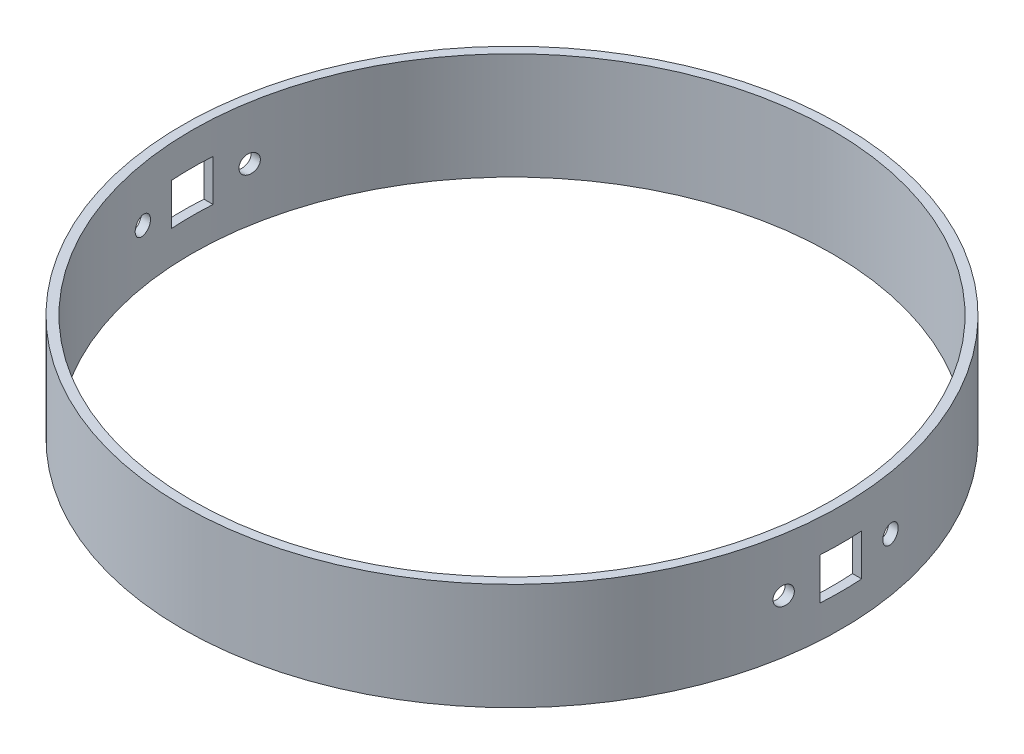
SolidWorks part; units mm, degrees
material "A-Glass Fiber"
ref_plane "Front Plane" through (0, 0, 0) normal (0, 0, 1) x (1, 0, 0)
ref_plane "Top Plane" through (0, 0, 0) normal (0, 1, 0) x (1, 0, 0)
ref_plane "Right Plane" through (0, 0, 0) normal (1, 0, 0) x (0, 0, -1)
sketch "Sketch1" plane through (0, 0, 0) normal (0, 1, 0) x (1, 0, 0)
  circle A0 centre (0, 0) radius 78.359
  circle A1 centre (0, 0) radius 76.1746
  dimension "D1" = 156.718
  dimension "D2" = 152.3492
extrude "Boss-Extrude1" add sketch "Sketch1" along normal blind 25.4
sketch "Sketch2" plane through (0, 0, 0) normal (1, 0, 0) x (0, 0, -1)
  line L0 (-78.359, 0) -> (78.359, 0) construction
  line L7 (0, 12.7) -> (0, 14.52) construction
  line L12 (4.953, 7.747) -> (-4.953, 7.747)
  line L13 (0, 25.4) -> (0, 0) construction
  line L14 (76.1746, 25.4) -> (-76.1746, 25.4) construction
  line L15 (-78.359, 0) -> (78.359, 0)
  line L16 (76.1746, 25.4) -> (-76.1746, 25.4)
  line L17 (-28.7231, 12.7) -> (26.1298, 12.7) construction
  line L25 (4.953, 7.747) -> (4.953, 17.653)
  line L26 (4.953, 17.653) -> (-4.953, 17.653)
  line L27 (-4.953, 7.747) -> (-4.953, 17.653)
  line L28 (4.953, 7.747) -> (-4.953, 17.653) construction
  line L29 (4.953, 17.653) -> (-4.953, 7.747) construction
  circle A0 centre (-12.7, 12.7) radius 2.1831
  circle A1 centre (12.7, 12.7) radius 2.1831
  point P0 (0, 9.85)
  point P14 (0, 3.175)
  point P27 (0, 12.7)
  dimension "D4" = 9.906
  dimension "D8" = 4.3663
  dimension "D1" = 12.7
  dimension "D5" = 9.906
extrude "Cut-Extrude1" cut sketch "Sketch2" along normal through all both and the other way through all contours L25 L12 L27 L26 | A1 | A0
ref_plane "Plane1" through (0, 0, 0) normal (0.9973, 0, 0.0728) x (0, -1, 0)
sketch "Sketch5" plane through (0, 0, 0) normal (0.9973, 0, 0.0728) x (0, -1, 0)
  line L0 (-13.35, 0.7076) -> (-13.35, 10.681) construction
  circle A0 centre (-20.335, 0) radius 2.75
  dimension "D1" = 5.5
  dimension "D2" = 6.985
extrude "Cut-Extrude2" [suppressed] cut sketch "Sketch5" along normal through all
ref_plane "Plane2" through (0, 12.7, 0) normal (0, 1, 0) x (1, 0, 0)
pattern_circular "CirPattern1" [suppressed] count 2 every 8.407 of bodies 104
mirror "Mirror2" about plane through (0, 0, 0) normal (1, 0, 0) of "Cut-Extrude1", "CirPattern1", "Boss-Extrude1" second plane through (0, 12.7, 0) second plane normal (0, 1, 0)
sketch "Sketch8" plane through (0, 0, 0) normal (1, 0, 0) x (0, 0, -1)
  line L0 (0, 25.4) -> (0, 0) construction
  line L1 (5, 15.225) -> (-5, 15.225)
  line L2 (5, 15.225) -> (5, 22.225)
  line L3 (5, 22.225) -> (-5, 22.225)
  line L4 (-5, 15.225) -> (-5, 22.225)
  line L5 (5, 15.225) -> (-5, 22.225) construction
  line L6 (5, 22.225) -> (-5, 15.225) construction
  line L8 (78.359, 25.4) -> (-78.359, 25.4) construction
  circle A0 centre (0, 6.335) radius 2.75
  point P0 (0, 18.725)
  dimension "D4" = 5.5
  dimension "D1" = 10
  dimension "D2" = 7
  dimension "D3" = 3.175
  dimension "D5" = 8.89
extrude "Cut-Extrude3" [suppressed] cut sketch "Sketch8" against normal through all
sketch "Sketch9" [suppressed] plane through (0, 0, 0) normal (0.9973, 0, 0.0728) x (0, -1, 0)
  line L0 (-15.225, -10.6344) -> (-15.225, -10.681) construction
  line L1 (-25.4, 0) -> (0, 0) construction
  circle A0 centre (-11.415, 0) radius 2.75
  dimension "D1" = 5.5
  dimension "D2" = 3.81
extrude "Cut-Extrude4" [suppressed] cut sketch "Sketch9" against normal through all
pattern_circular "CirPattern2" [suppressed] count 2 every 8.41 of bodies 109
equation "\"Mid_Tube_Length\"= 1in"
equation "\"Bodytube_OD\" = 6.17in"
equation "\"Bodytube_ID\" = 5.998in"
equation "\"D1@Sketch1\"=\"Bodytube_OD\""
equation "\"D2@Sketch1\"= \"Bodytube_ID\""
equation "\"Camera_Cutout_Width\"=10mm"
equation "\"Camera_Cutout_Height\"=7mm"
equation "\"Fwd_Tube_Length\" = 40in"
equation "\"BKHD_Screw_Diam\"= 3.5mm"
equation "\"Fwd_BKHD_From_Top\" = 18in"
equation "\"Shear_Screw_Diameter\" = 0.086in"
equation "\"Shear_Screw_Coupler_Location\" = 4.5in"
equation "\"Motor_OD\" = 4in"
equation "\"Mid_Coupler_Length\" = 13in"
equation "\"Aft_Section_Length\"= 39in"
equation "\"AB_Coupler_OD_Length\"= 1in"
equation "\"AB_Coupling_Section_Length\"= 0.375in"
equation "\"AB_Coupler_Length\"= \"AB_Coupler_OD_Length\" + \"AB_Coupling_Section_Length\" * 2"
equation "\"Cutout_Angle\" = 80"
equation "\"AB_Paddle_Height\" = 0.375in"
equation "\"AB_Coupler_Num_Screws\"= 4"
equation "\"AB_BKHD_Thickness\" = 0.375in"
equation "\"AB_Mount_From_Bottom\" = 23.175in"
equation "\"Num_Cutouts\" = 3"
equation "\"AB_Coupler_OD\"= 6.17in"
equation "\"AB_Coupler_ID\"= 5.75in"
equation "\"AB_Coupler_Surface_Diameter\"= 5.998in"
equation "\"AB_Coupling_Screw_Diameter\"= 0.15748in"
equation "\"AB_Central_Bushing_Length\" = .4724in"
equation "\"Lead_Screw_Dist\" = 3.4in"
equation "\"Lead_Screw_Diam\" = 0.386in"
equation "\"Lead_Screw_Length\" = (\"Mid_Coupler_Length\" + 2*0.375in + 2*0.5in)"
equation "\"Paddle_Pin_Offset\" = .25in"
equation "\"Paddle_Pin_Radius\" = 2.25in"
equation "\"SS_Paddle_Pin_Radius\" = 2.25*0.66in"
equation "\"Paddle_Gear_OD\" = 3.2in"
equation "\"Drive_Gear_OD\" = 1.7in"
equation "\"Fin_Thickness\"= .118in"
equation "\"Guiderail_Cutout_Diameter\"= 1.5in"
equation "\"DB9_Hole_Dist\" = 25mm"
equation "\"DB9_Relief_Width\" = 0.47in"
equation "\"DB9_Relief_Hole_Offset\" = 0.09in"
equation "\"Airbrakes_Wire_Hole_Dia\" = .25in"
equation "\"Airbrakes_Wire_Hole_Dist\" = 1.1in"
equation "\"Servo_Gear_Offset\" = 0.5in"
equation "\"FWD_Shear_Screw_Dist\" = 1.5in"
equation "\"Camera_Screw_Dia\" = 0.216535"
equation "\"D1@Sketch5\"=\"Camera_Screw_Dia\""
equation "\"Camera_Hole_Angle\" = atn ( 2 / 3 * tan ( 12.5deg ) )"
equation "\"D2@CirPattern1\"=\"Camera_Hole_Angle\""
equation "\"D4@Sketch8\"=\"Camera_Screw_Dia\""
equation "\"D1@Sketch9\"=\"Camera_Screw_Dia\""
